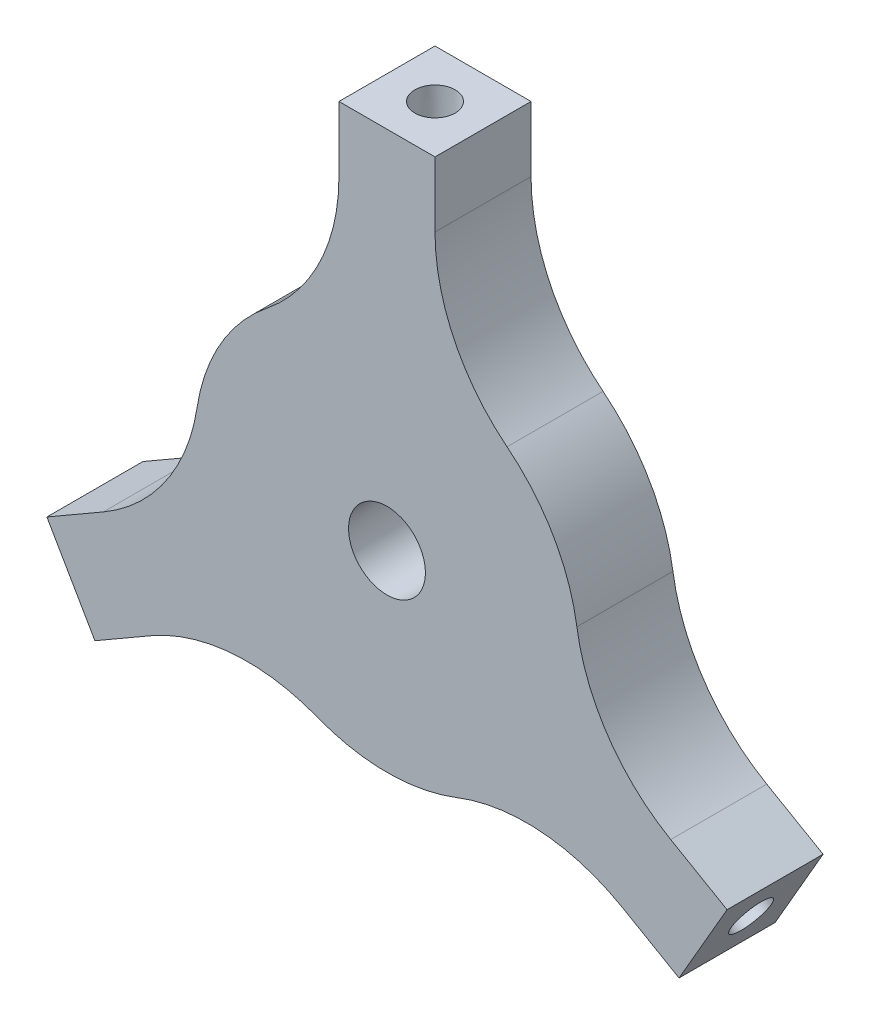
SolidWorks part; units mm, degrees
ref_plane "Front Plane" through (0, 0, 0) normal (0, 0, 1) x (1, 0, 0)
ref_plane "Top Plane" through (0, 0, 0) normal (0, 1, 0) x (1, 0, 0)
ref_plane "Right Plane" through (0, 0, 0) normal (1, 0, 0) x (0, 0, -1)
sketch "Sketch1" plane through (0, 0, 0) normal (0, 0, 1) x (1, 0, 0)
  line L5 (7.1353, -7.0063) -> (15.2045, -11.6651)
  line L6 (9.6353, -2.6762) -> (17.7045, -7.3349)
  line L7 (15.2045, -11.6651) -> (17.7045, -7.3349)
  line L9 (-9.6353, -2.6762) -> (-17.7045, -7.3349)
  line L10 (-7.1353, -7.0063) -> (-15.2045, -11.6651)
  line L11 (-17.7045, -7.3349) -> (-15.2045, -11.6651)
  line L13 (-2.5, 9.6825) -> (-2.5, 19)
  line L14 (2.5, 9.6825) -> (2.5, 19)
  line L15 (-2.5, 19) -> (2.5, 19)
  line L16 (-9.6353, -2.6762) -> (-2.5, 9.6825) construction
  line L17 (2.5, 9.6825) -> (9.6353, -2.6762) construction
  line L18 (-7.1353, -7.0063) -> (7.1353, -7.0063) construction
  line L19 (2.5, 19) -> (17.7045, -7.3349) construction
  line L20 (15.2045, -11.6651) -> (-15.2045, -11.6651) construction
  line L21 (-17.7045, -7.3349) -> (-2.5, 19) construction
  arc A0 (9.6353, -2.6762) -> (2.5, 9.6825) centre (0, 0) ccw
  arc A1 (-2.5, 9.6825) -> (-9.6353, -2.6762) centre (0, 0) ccw
  arc A2 (-7.1353, -7.0063) -> (7.1353, -7.0063) centre (0, 0) ccw
  dimension "D1" = 20
  dimension "D2" = 5
  dimension "D3" = 19
extrude "Boss-Extrude1" add sketch "Sketch1" along normal blind 5
sketch "Sketch2" plane through (0, 19, 0) normal (0, 1, 0) x (1, 0, 0)
  line L0 (0, 0) -> (0, -2.5) construction
  line L1 (0, -2.5) -> (2.5, -2.5) construction
  line L2 (2.5, -5) -> (2.5, 0) construction
  circle A0 centre (0, -2.5) radius 1.05
  dimension "D1" = 2.1
extrude "Cut-Extrude1" cut sketch "Sketch2" against normal blind 10
pattern_circular "CirPattern2" count 3 over 360 about axis through (0, 0, 5) along (0, 0, -1) of "Cut-Extrude1"
draft "Draft4" type of draft neutral plane draft angle 1 faces to draft 1 face at (0, 9, 3.55) neutral plane through (-2.5, 19, 5) neutral plane normal (0, 1, 0) parameters "D1"=1
draft "Draft5" type of draft neutral plane draft angle 1 faces to draft 1 face at (-7.7942, -4.5, 3.55) neutral plane through (-17.7045, -7.3349, 5) neutral plane normal (-0.866, -0.5, 0) parameters "D1"=1
draft "Draft6" type of draft neutral plane draft angle 1 faces to draft 1 face at (7.7942, -4.5, 3.55) neutral plane through (15.2045, -11.6651, 5) neutral plane normal (0.866, -0.5, 0) parameters "D1"=1
sketch "Sketch3" plane through (0, 0, 0) normal (0, 0, -1) x (-1, 0, 0)
  circle A0 centre (0, 0) radius 2
  dimension "D1" = 4
extrude "Cut-Extrude2" cut sketch "Sketch3" against normal through all
fillet "Fillet1" radius 10 6 edges at (2.5, 9.6825, 2.5) (9.6353, -2.6762, 2.5) (7.1353, -7.0063, 2.5) (-7.1353, -7.0063, 2.5) (-9.6353, -2.6762, 2.5) (-2.5, 9.6825, 2.5)
